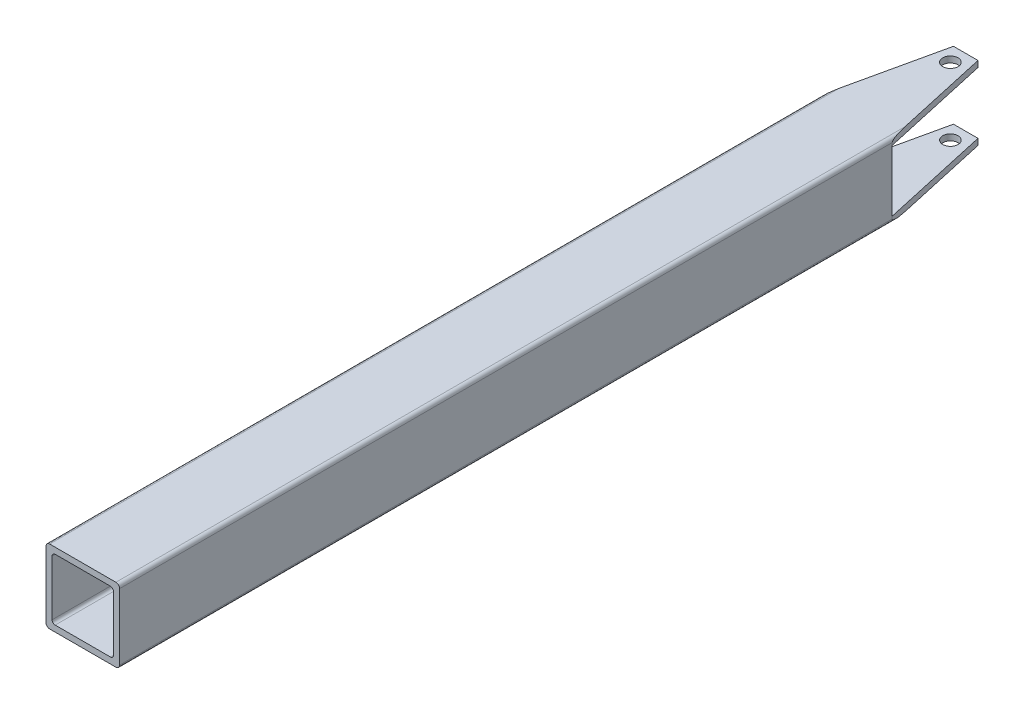
SolidWorks part; units mm, degrees
ref_plane "Front" through (0, 0, 0) normal (0, 0, 1) x (1, 0, 0)
ref_plane "Top" through (0, 0, 0) normal (0, 1, 0) x (1, 0, 0)
ref_plane "Right" through (0, 0, 0) normal (1, 0, 0) x (0, 0, -1)
sketch "Sketch1" plane through (0, 0, 0) normal (0, 0, 1) x (1, 0, 0)
  line L0 (-31.75, 0) -> (-38.1, 0) construction
  line L1 (34.29, -38.1) -> (-34.29, -38.1)
  line L2 (38.1, -34.29) -> (38.1, 34.29)
  line L3 (34.29, 38.1) -> (-34.29, 38.1)
  line L4 (-38.1, -34.29) -> (-38.1, 34.29)
  line L5 (38.1, -38.1) -> (-38.1, 38.1) construction
  line L6 (38.1, 38.1) -> (-38.1, -38.1) construction
  line L7 (28.575, 31.75) -> (-28.575, 31.75)
  line L8 (31.75, 28.575) -> (31.75, -28.575)
  line L9 (28.575, -31.75) -> (-28.575, -31.75)
  line L10 (-31.75, 28.575) -> (-31.75, -28.575)
  line L11 (31.75, 31.75) -> (-31.75, -31.75) construction
  line L12 (31.75, -31.75) -> (-31.75, 31.75) construction
  line L13 (0, -31.75) -> (0, -38.1) construction
  line L14 (31.75, -28.575) -> (31.75, -38.1) construction
  line L16 (31.75, -38.1) -> (38.1, -38.1) construction
  arc A0 (-28.575, -31.75) -> (-31.75, -28.575) centre (-28.575, -28.575) cw
  arc A1 (31.75, -28.575) -> (28.575, -31.75) centre (28.575, -28.575) cw
  arc A2 (28.575, 31.75) -> (31.75, 28.575) centre (28.575, 28.575) cw
  arc A3 (-28.575, 31.75) -> (-31.75, 28.575) centre (-28.575, 28.575) ccw
  arc A4 (34.29, -38.1) -> (38.1, -34.29) centre (34.29, -34.29) ccw
  arc A5 (38.1, 34.29) -> (34.29, 38.1) centre (34.29, 34.29) ccw
  arc A6 (-34.29, 38.1) -> (-38.1, 34.29) centre (-34.29, 34.29) ccw
  arc A7 (-34.29, -38.1) -> (-38.1, -34.29) centre (-34.29, -34.29) cw
  point P0 (0, 0)
  point P6 (0, 0)
  dimension "D2" = 3.175
  dimension "D3" = 3.81
sketch "Sketch2" plane through (0, 0, 0) normal (1, 0, 0) x (0, 0, -1)
  line L0 (-457.2, 0) -> (457.2, 0) construction
  dimension "Length" = 914.4
ref_plane "Plane1" through (38.1, 0, 0) normal (1, 0, 0) x (0, 0, -1)
sketch "Sketch5" plane through (38.1, 0, 0) normal (1, 0, 0) x (0, 0, -1)
  line L0 (-457.2, 38.1) -> (-457.2, -38.1) construction
  line L1 (457.2, 38.1) -> (457.2, -38.1) construction
sketch "Sketch4" plane through (0, 0, 0) normal (0, 0, 1) x (1, 0, 0)
  line L0 (38.1, -34.29) -> (38.1, 34.29) construction
  line L1 (34.29, 38.1) -> (-34.29, 38.1) construction
  line L2 (-38.1, -34.29) -> (-38.1, 34.29) construction
  line L3 (34.29, -38.1) -> (-34.29, -38.1) construction
  line L4 (31.75, 28.575) -> (31.75, -28.575) construction
  line L5 (28.575, -31.75) -> (-28.575, -31.75) construction
  line L6 (-31.75, 28.575) -> (-31.75, -28.575) construction
  line L7 (28.575, 31.75) -> (-28.575, 31.75) construction
  line L8 (38.1, -34.29) -> (38.1, 34.29)
  line L9 (34.29, 38.1) -> (-34.29, 38.1)
  line L10 (-38.1, -34.29) -> (-38.1, 34.29)
  line L11 (34.29, -38.1) -> (-34.29, -38.1)
  line L12 (31.75, 28.575) -> (31.75, -28.575)
  line L13 (28.575, -31.75) -> (-28.575, -31.75)
  line L14 (-31.75, 28.575) -> (-31.75, -28.575)
  line L15 (28.575, 31.75) -> (-28.575, 31.75)
  arc A0 (38.1, 34.29) -> (34.29, 38.1) centre (34.29, 34.29) ccw construction
  arc A1 (-34.29, 38.1) -> (-38.1, 34.29) centre (-34.29, 34.29) ccw construction
  arc A2 (-38.1, -34.29) -> (-34.29, -38.1) centre (-34.29, -34.29) ccw construction
  arc A3 (34.29, -38.1) -> (38.1, -34.29) centre (34.29, -34.29) ccw construction
  arc A4 (28.575, -31.75) -> (31.75, -28.575) centre (28.575, -28.575) ccw construction
  arc A5 (-31.75, -28.575) -> (-28.575, -31.75) centre (-28.575, -28.575) ccw construction
  arc A6 (-28.575, 31.75) -> (-31.75, 28.575) centre (-28.575, 28.575) ccw construction
  arc A7 (31.75, 28.575) -> (28.575, 31.75) centre (28.575, 28.575) ccw construction
  arc A8 (38.1, 34.29) -> (34.29, 38.1) centre (34.29, 34.29) ccw
  arc A9 (-34.29, 38.1) -> (-38.1, 34.29) centre (-34.29, 34.29) ccw
  arc A10 (-38.1, -34.29) -> (-34.29, -38.1) centre (-34.29, -34.29) ccw
  arc A11 (34.29, -38.1) -> (38.1, -34.29) centre (34.29, -34.29) ccw
  arc A12 (28.575, -31.75) -> (31.75, -28.575) centre (28.575, -28.575) ccw
  arc A13 (-31.75, -28.575) -> (-28.575, -31.75) centre (-28.575, -28.575) ccw
  arc A14 (-28.575, 31.75) -> (-31.75, 28.575) centre (-28.575, 28.575) ccw
  arc A15 (31.75, 28.575) -> (28.575, 31.75) centre (28.575, 28.575) ccw
extrude "Boss-Extrude1" add sketch "Sketch4" along normal up to vertex (457.2 mm away) and the other way up to vertex (457.2 mm away) up to point (0, 0, 457.2) other way up to point (0, 0, -457.2)
sketch "Sketch6" plane through (-38.1, 0, 0) normal (-1, 0, 0) x (0, 0, 1)
  line L0 (-457.2, -31.75) -> (-371.4675, -31.75) construction
  line L1 (-457.2, 31.75) -> (-342.9, 31.75)
  line L2 (-457.2, 31.75) -> (-457.2, -31.75)
  line L3 (-457.2, -31.75) -> (-342.9, -31.75)
  line L4 (-342.9, 31.75) -> (-342.9, -31.75)
  point P5 (-457.2, -31.75)
  dimension "D1" = 114.3
extrude "side cut" cut sketch "Sketch6" against normal through all
sketch "Sketch7" plane through (0, -38.1, 0) normal (0, -1, 0) x (1, 0, 0)
  line L0 (0, -457.2) -> (0, -341.7828) construction
  line L1 (-34.29, -457.2) -> (34.29, -457.2) construction
  line L2 (-38.1, -342.9) -> (-38.1, -457.2)
  line L3 (-38.1, -457.2) -> (-12.7, -457.2)
  line L4 (-12.7, -457.2) -> (-38.1, -342.9)
  line L5 (12.7, -457.2) -> (38.1, -342.9)
  line L6 (38.1, -457.2) -> (12.7, -457.2)
  line L7 (38.1, -342.9) -> (38.1, -457.2)
  dimension "D1" = 25.4
extrude "triangle cut" cut sketch "Sketch7" against normal through all
sketch "Sketch8" plane through (0, 38.1, 0) normal (0, 1, 0) x (1, 0, 0)
  line L0 (0, 457.2) -> (0, 353.4841) construction
  line L1 (12.7, 457.2) -> (-12.7, 457.2) construction
  circle A0 centre (0, 441.325) radius 7.9375
  dimension "D1" = 15.875
  dimension "D2" = 15.875
extrude "Cut-Extrude4" cut sketch "Sketch8" against normal through all
sketch "Sketch9" plane through (38.1, 0, 0) normal (1, 0, 0) x (0, 0, -1)
  line L0 (433.3875, 34.925) -> (449.2625, 34.925) construction
  line L1 (433.3875, 38.1) -> (433.3875, 31.75) construction
  line L2 (449.2625, 31.75) -> (449.2625, 38.1) construction
  line L3 (433.3875, -34.925) -> (449.2625, -34.925) construction
  line L4 (433.3875, -31.75) -> (433.3875, -38.1) construction
  line L5 (449.2625, -38.1) -> (449.2625, -31.75) construction
  line L6 (441.325, -34.925) -> (441.325, 34.925) construction
  line L7 (441.325, 0) -> (-53.975, 0)
  point P18 (-53.975, 0)
  dimension "D1" = 495.3
equation "\"D3@Sketch1\"=\"Outside Width@Sketch1\"*.05"
equation "\"D2@Sketch1\"=\"D1@Sketch1\"*.05"
equation "\"mountingPointDistance\"=19.5"
equation "\"D1@Sketch9\"=\"mountingPointDistance\""
